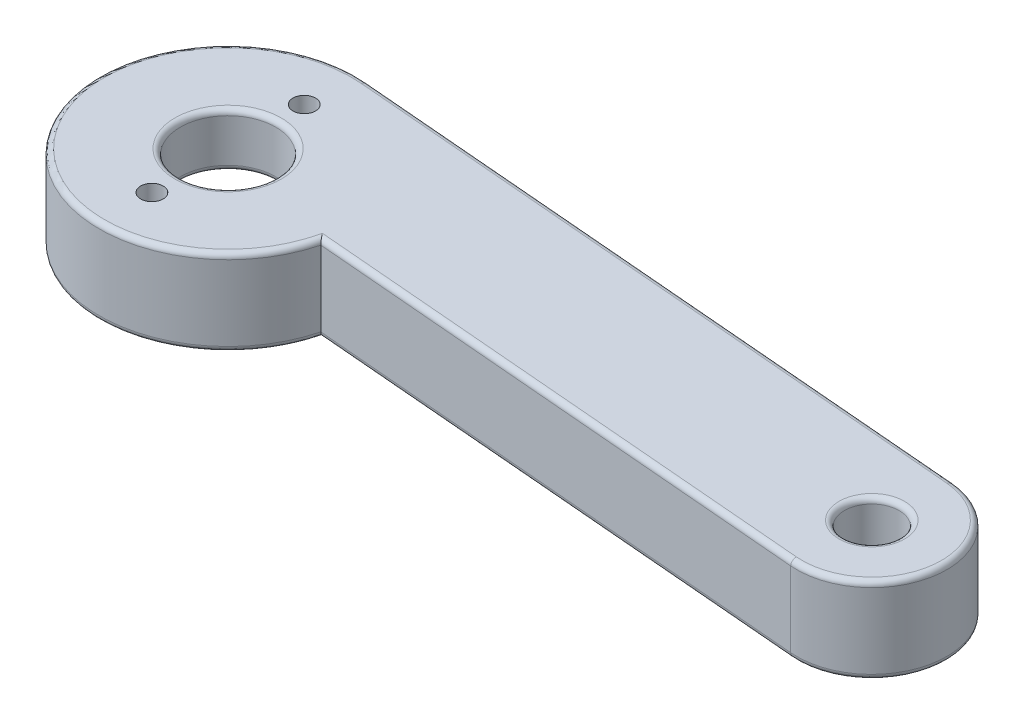
SolidWorks part; units mm, degrees
ref_plane "前视基准面" through (0, 0, 0) normal (0, 0, 1) x (1, 0, 0)
ref_plane "上视基准面" through (0, 0, 0) normal (0, 1, 0) x (1, 0, 0)
ref_plane "右视基准面" through (0, 0, 0) normal (1, 0, 0) x (0, 0, -1)
other "Configuration Table"
sketch "草图1" plane through (0, 0, 0) normal (0, 1, 0) x (1, 0, 0)
  line L0 (0, 0) -> (60, 0) construction
  line L1 (1, 11.9583) -> (60.5833, 6.9757)
  line L3 (59.4167, -6.9757) -> (11.6243, -2.9791)
  arc A0 (1, 11.9583) -> (11.6243, -2.9791) centre (0, 0) ccw
  arc A1 (60.5833, 6.9757) -> (59.4167, -6.9757) centre (60, 0) cw
  dimension "D2" = 7
  dimension "D3" = 12
  dimension "D1" = 60
extrude "凸台-拉伸1" add sketch "草图1" along normal blind 8
ref_axis "主基准轴" through (0, 8, 0) along (0, -1, 0)
ref_axis "前基准轴" through (60, 8, 0) along (0, -1, 0)
sketch "草图2" plane through (0, 0, 0) normal (0, 1, 0) x (1, 0, 0)
  circle A0 centre (0, 0) radius 10.5
  dimension "D1" = 21
extrude "切除-拉伸1" cut sketch "草图2" along normal blind 3
sketch "草图3" plane through (0, 3, 0) normal (0, -1, 0) x (1, 0, 0)
  line L1 (0, 0) -> (-15.5402, 0) construction
  circle A0 centre (0, 0) radius 4.45
  circle A2 centre (0, -7.1) radius 1.05
  circle A3 centre (0, 7.1) radius 1.05
  dimension "D1" = 8.9
  dimension "D2" = 2.1
  dimension "D3" = 7.1
extrude "切除-拉伸2" cut sketch "草图3" against normal through all
sketch "草图4" plane through (0, 0, 0) normal (0, -1, 0) x (1, 0, 0)
  circle A0 centre (60, 0) radius 2.55
  dimension "D1" = 5.1
extrude "切除-拉伸3" cut sketch "草图4" against normal through all
fillet "圆角1" radius 0.5 8 edges at (35.5205, 8, 4.9774) (66.9757, 8, 0.5833) (30.7917, 8, -9.467) (35.5205, 0, 4.9774) (66.9757, 0, 0.5833) (-9.7788, 0, 6.9553) (-9.7788, 8, 6.9553) (30.7917, 0, -9.467)
fillet "圆角2" radius 0.5 4 edges at (0, 3, -4.45) (0, 8, -4.45) (60, 8, -2.55) (60, 0, -2.55)
